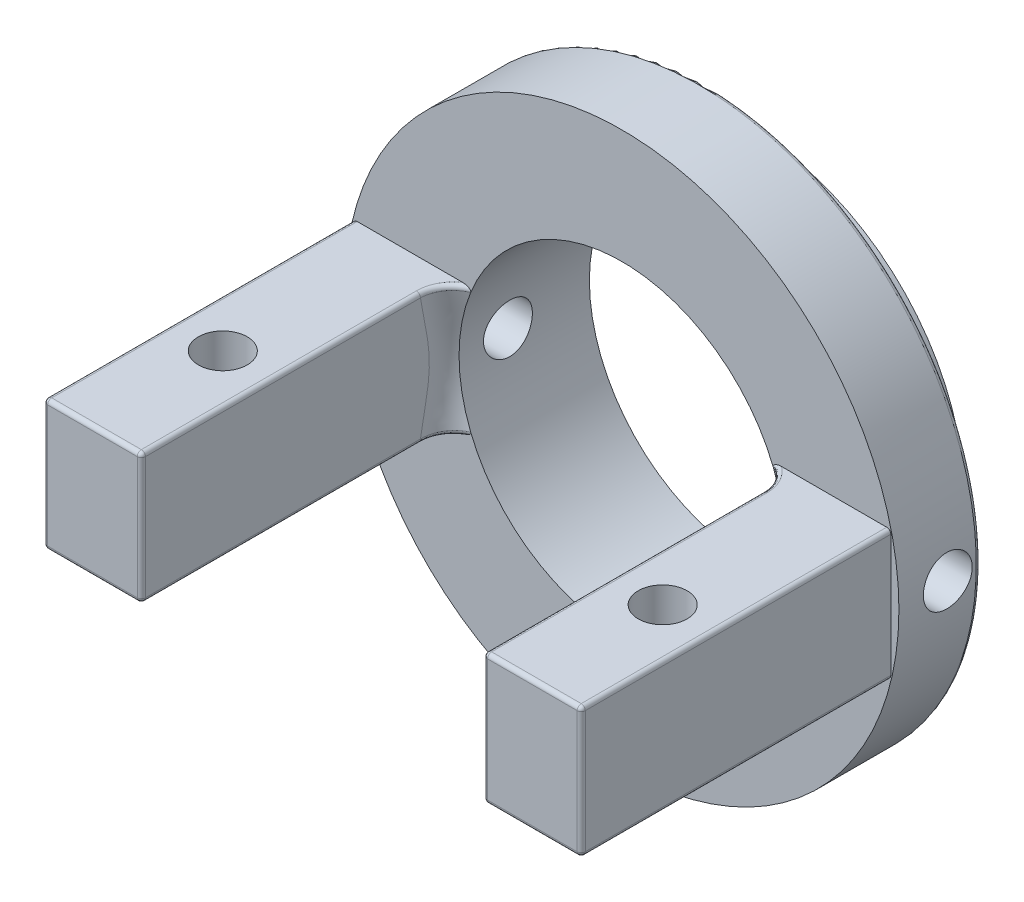
SolidWorks part; units mm, degrees
ref_plane "Front Plane" through (0, 0, 0) normal (0, 0, 1) x (1, 0, 0)
ref_plane "Top Plane" through (0, 0, 0) normal (0, 1, 0) x (1, 0, 0)
ref_plane "Right Plane" through (0, 0, 0) normal (1, 0, 0) x (0, 0, -1)
sketch "Sketch1" plane through (0, 0, 0) normal (0, 0, 1) x (1, 0, 0)
  circle A0 centre (0, 0) radius 17
  circle A1 centre (0, 0) radius 10
  dimension "D1" = 34
  dimension "D2" = 20
extrude "Boss-Extrude1" add sketch "Sketch1" along normal blind 8
sketch "Sketch6" plane through (0, 0, 8) normal (0, 0, 1) x (1, 0, 0)
  line L1 (-16.5, 4) -> (-10.5, 4)
  line L2 (-16.5, 4) -> (-16.5, -4)
  line L3 (-16.5, -4) -> (-10.5, -4)
  line L4 (-10.5, 4) -> (-10.5, -4)
  point P4 (-10.5, 0)
  dimension "D1" = 4
  dimension "D2" = 10.5
  dimension "D3" = 16.5
extrude "Boss-Extrude2" add sketch "Sketch6" along normal blind 19
sketch "Sketch7" plane through (0, 4, 0) normal (0, 1, 0) x (1, 0, 0)
  line L2 (-10.5, -8) -> (-16.5, -8) construction
  line L3 (-10.5, -27) -> (-16.5, -27) construction
  circle A0 centre (-13.5, -19) radius 1.5
  point P6 (-14.3053, -8)
  dimension "D1" = 3
  dimension "D2" = 11
  dimension "D3" = 8
  dimension "D4" = 13.5
extrude "Cut-Extrude5" cut sketch "Sketch7" against normal through all
mirror "Mirror1" about plane through (0, 0, 0) normal (1, 0, 0) of "Boss-Extrude2", "Cut-Extrude5"
sketch "Sketch8" plane through (0, 0, 0) normal (0, 0, -1) x (-1, 0, 0)
  circle A0 centre (0, 0) radius 13
  circle A1 centre (0, 0) radius 17 construction
  circle A2 centre (0, 0) radius 17
  dimension "D1" = 26
extrude "Cut-Extrude6" cut sketch "Sketch8" against normal blind 3
fillet "Fillet1" radius 2 1 edges at (-13, 0, 3)
sketch "Sketch10" plane through (0, 0, 0) normal (1, 0, 0) x (0, 0, -1)
  circle A0 centre (-5, 0) radius 1.5
  point P2 (0, 0)
  dimension "D1" = 3
  dimension "D2" = 5
extrude "Cut-Extrude7" cut sketch "Sketch10" against normal through all both and the other way through all
fillet "Fillet2" radius 0.25 1 edges at (-17, 0, 3)
fillet "Fillet3" radius 2 2 edges at (-10.5, 0, 8) (10.5, 0, 8)
fillet "Fillet4" radius 0.25 20 edges at (10.0539, -4, 8.6343) (10.1947, 4, 8.8334) (-10.1947, -4, 8.8334) (-10.0539, 4, 8.6343) (16.5, -4, 17.5) (16.5, 4, 17.5) (16.5, 0, 27) (10.5, -4, 18.453) (13.5, -4, 27) (10.5, 0, 27) (13.5, 4, 27) (10.5, 4, 18.453) (-10.5, -4, 18.453) (-10.5, 4, 18.453) (-10.5, 0, 27) (-13.5, 4, 27) (-13.5, -4, 27) (-16.5, -4, 17.5) (-16.5, 4, 17.5) (-16.5, 0, 27)
